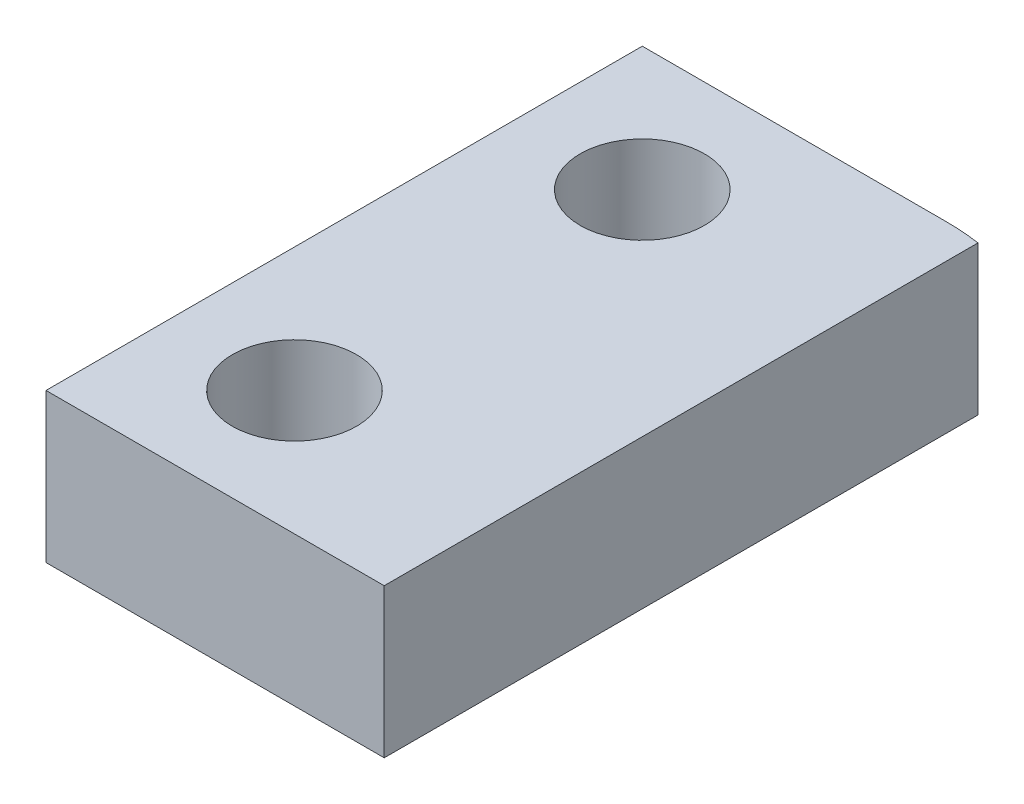
SolidWorks part; units mm, degrees
ref_plane "Front Plane" through (0, 0, 0) normal (0, 0, 1) x (1, 0, 0)
ref_plane "Top Plane" through (0, 0, 0) normal (0, 1, 0) x (1, 0, 0)
ref_plane "Right Plane" through (0, 0, 0) normal (1, 0, 0) x (0, 0, -1)
sketch "Sketch1" plane through (0, 0, 0) normal (0, 1, 0) x (1, 0, 0)
  line L1 (20, -6) -> (-20, -6)
  line L2 (20, -6) -> (20, 6)
  line L3 (20, 6) -> (-20, 6)
  line L4 (-20, -6) -> (-20, 6)
  line L5 (20, -6) -> (-20, 6) construction
  line L6 (20, 6) -> (-20, -6) construction
  point P0 (0, 0)
  dimension "D1" = 12
  dimension "D2" = 40
extrude "Boss-Extrude1" add sketch "Sketch1" along normal blind 3
sketch "Sketch3" plane through (0, 3, 0) normal (0, 1, 0) x (1, 0, 0)
  line L0 (-20, 6) -> (-20, -6) construction
  line L1 (20, 6) -> (-20, 6) construction
  line L2 (-20, -6) -> (20, -6) construction
  circle A0 centre (-17.5, 3.5) radius 1.25
  circle A1 centre (-17.5, -3.5) radius 1.25
  dimension "D1" = 2.5
  dimension "D3" = 2.5
  dimension "D4" = 2.5
  dimension "D5" = 2.5
  dimension "D2" = 2.5
  dimension "D6" = 2.5
extrude "Cut-Extrude2" cut sketch "Sketch3" against normal through all
sketch "Sketch5" plane through (0, 3, 0) normal (0, 1, 0) x (1, 0, 0)
  line L0 (-13.4582, 6) -> (20, 0)
  line L2 (20, 6) -> (-20, 6) construction
  line L3 (20, -6) -> (20, 6) construction
  line L4 (20, 0) -> (20, -6)
  line L5 (20, -6) -> (17.0301, -6)
  line L6 (-20, -6) -> (20, -6) construction
  line L7 (-2.1446, -4.2501) -> (-6.5697, -6)
  line L8 (-6.5697, -6) -> (-13.4582, -6)
  line L9 (-13.4582, -6) -> (-13.4582, -10.2372)
  line L10 (-13.4582, -10.2372) -> (26.0235, -9.7269)
  line L11 (26.0235, -9.7269) -> (26.0235, 8.4773)
  line L12 (26.0235, 8.4773) -> (-13.4582, 8.4773)
  line L13 (-13.4582, 8.4773) -> (-13.4582, 6)
  arc A0 (17.0301, -6) -> (-2.1446, -4.2501) centre (5.8843, -22.2017) ccw
extrude "Cut-Extrude3" cut sketch "Sketch5" against normal blind 10
fillet "Fillet2" radius 5 3 edges at (17.0301, 1.5, 6) (-2.1446, 1.5, 4.2501) (-6.5697, 1.5, 6)
fillet "Fillet3" radius 1 1 edges at (20, 1.5, 6)
fillet "Fillet4" radius 5 1 edges at (20, 1.5, 0)
fillet "Fillet5" radius 5 1 edges at (-13.4582, 1.5, -6)
sketch "Sketch6" plane through (0, 3, 0) normal (0, 1, 0) x (1, 0, 0)
  line L1 (-13.1937, 9.5737) -> (22.7605, 9.5737)
  line L2 (-13.1937, 9.5737) -> (-13.1937, -16.2924)
  line L3 (-13.1937, -16.2924) -> (22.7605, -16.2924)
  line L4 (22.7605, 9.5737) -> (22.7605, -16.2924)
extrude "Cut-Extrude4" cut sketch "Sketch6" against normal blind 10
